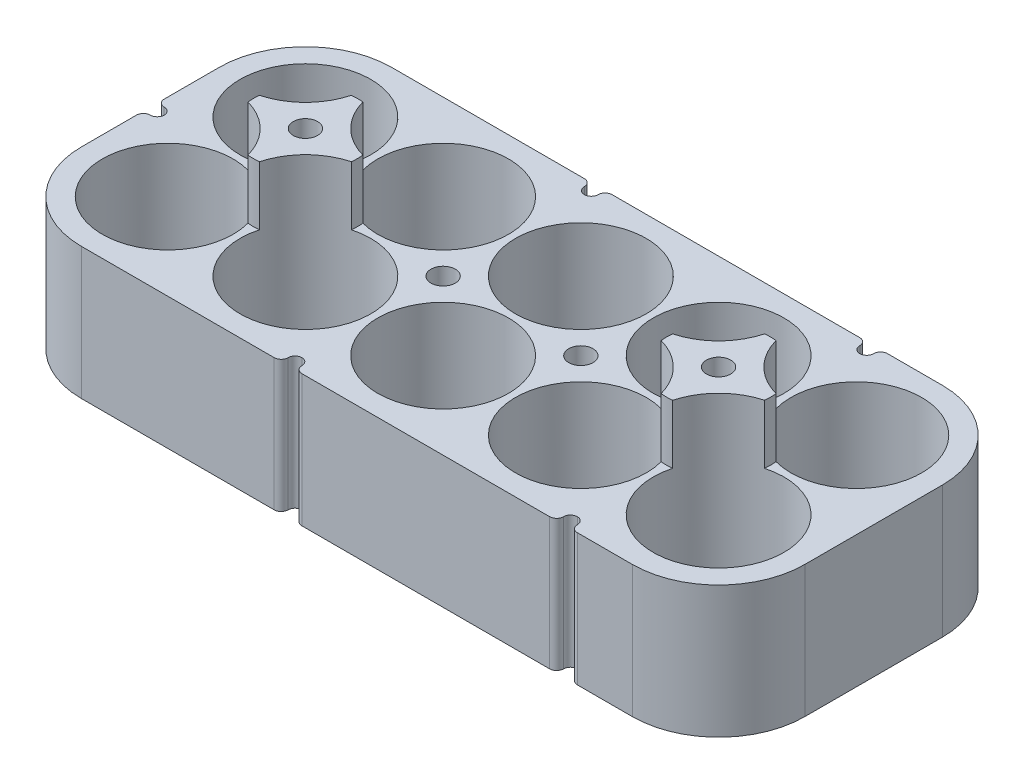
SolidWorks part; units mm, degrees
ref_plane "Front Plane" through (0, 0, 0) normal (0, 0, 1) x (1, 0, 0)
ref_plane "Top Plane" through (0, 0, 0) normal (0, 1, 0) x (1, 0, 0)
ref_plane "Right Plane" through (0, 0, 0) normal (1, 0, 0) x (0, 0, -1)
sketch "Sketch2" plane through (0, 0, 0) normal (0, 1, 0) x (1, 0, 0)
  line L0 (-39.7, 9.925) -> (-19.85, 9.925) construction
  line L1 (-19.85, 9.925) -> (0, 9.925) construction
  line L2 (0, 9.925) -> (19.85, 9.925) construction
  line L3 (19.85, 9.925) -> (39.7, 9.925) construction
  line L4 (39.7, 9.925) -> (39.7, -9.925) construction
  line L5 (39.7, -9.925) -> (19.85, -9.925) construction
  line L6 (19.85, -9.925) -> (0, -9.925) construction
  line L7 (0, -9.925) -> (-19.85, -9.925) construction
  line L8 (-39.7, 9.925) -> (-39.7, -9.925) construction
  line L9 (-39.7, -9.925) -> (-19.85, -9.925) construction
  line L10 (-39.7, 9.925) -> (39.7, -9.925) construction
  line L11 (-30.275, 9.925) -> (-29.275, 9.925) construction
  line L16 (-39.7, 0.5) -> (-39.7, -0.5) construction
  line L17 (-39.7, 22.35) -> (39.7, 22.35)
  line L19 (52.125, -9.925) -> (52.125, 9.925)
  line L20 (39.7, -22.35) -> (-39.7, -22.35)
  line L21 (-52.125, -9.925) -> (-52.125, 9.925)
  line L22 (-39.7, -9.925) -> (-52.125, -9.925) construction
  circle A0 centre (-39.7, 9.925) radius 9.425
  circle A1 centre (-19.85, 9.925) radius 9.425
  circle A2 centre (-39.7, -9.925) radius 9.425
  circle A3 centre (-19.85, -9.925) radius 9.425
  circle A4 centre (0, 9.925) radius 9.425
  circle A5 centre (0, -9.925) radius 9.425
  circle A6 centre (19.85, 9.925) radius 9.425
  circle A7 centre (19.85, -9.925) radius 9.425
  circle A8 centre (39.7, 9.925) radius 9.425
  circle A9 centre (39.7, -9.925) radius 9.425
  circle A10 centre (-39.7, 9.925) radius 12.425
  circle A11 centre (-39.7, -9.925) radius 12.425
  circle A12 centre (39.7, -9.925) radius 12.425
  circle A13 centre (39.7, 9.925) radius 12.425
  dimension "D1" = 18.85
  dimension "D2" = 1
  dimension "D3" = 1
  dimension "D4" = 3
extrude "Boss-Extrude1" add sketch "Sketch2" along normal blind 2.5 contours A13 L17 A10 A1 A11 A3 L20 A12 A7 A6 A5 A4 | A12 A13 A6 A8 | A13 A9 A12 A7 | A13 A12 L19 | A9 A13 A12 A8 | A11 A10 L21 | A11 A10 A1 A0 | A3 A11 A10 A2 | A10 A11 A0 A2 region at (-32.8744, 0, -19.9125) region at (0, 0, 0) region at (48.2539, 0, -18.4789) region at (-50.7094, 0, 0) region at (50.7094, 0, 0) region at (-50.5254, 0, 4.5259) region at (-39.7, 0, 0) region at (48.2539, 0, 18.4789) region at (39.7, 0, 0)
sketch "Sketch7" plane through (0, 0, 0) normal (0, 1, 0) x (1, 0, 0)
  line L0 (-29.775, 0) -> (-9.925, 0) construction
  line L1 (-9.925, 0) -> (9.925, 0) construction
  line L2 (9.925, 0) -> (29.775, 0) construction
  circle A1 centre (-29.775, 0) radius 3
  circle A2 centre (-9.925, 0) radius 1.75
  circle A3 centre (9.925, 0) radius 1.75
  circle A4 centre (29.775, 0) radius 3
  circle A5 centre (-29.775, 0) radius 4.6111 construction
  circle A7 centre (-39.7, 9.925) radius 9.425 construction
  circle A8 centre (-19.85, -9.925) radius 9.425 construction
  dimension "D1" = 6
  dimension "D2" = 3.5
extrude "Cut-Extrude3" cut sketch "Sketch7" along normal through all both and the other way through all
sketch "Sketch9" plane through (0, 2.5, 0) normal (0, 1, 0) x (1, 0, 0)
  line L0 (39.7, -22.35) -> (-39.7, -22.35)
  line L1 (-52.125, -9.925) -> (-52.125, 9.925)
  line L2 (-39.7, 22.35) -> (39.7, 22.35)
  line L3 (52.125, 9.925) -> (52.125, -9.925)
  line L4 (6.4609, 0) -> (-6.4609, 0) construction
  line L5 (6.4609, 0) -> (8.1929, -3)
  line L6 (8.1929, -3) -> (11.6571, -3)
  line L7 (11.6571, -3) -> (13.3891, 0)
  line L8 (13.3891, 0) -> (11.6571, 3)
  line L9 (11.6571, 3) -> (8.1929, 3)
  line L10 (8.1929, 3) -> (6.4609, 0)
  line L11 (-6.4609, 0) -> (-8.1929, 3)
  line L12 (-8.1929, 3) -> (-11.6571, 3)
  line L13 (-11.6571, 3) -> (-13.3891, 0)
  line L14 (-13.3891, 0) -> (-11.6571, -3)
  line L15 (-11.6571, -3) -> (-8.1929, -3)
  line L16 (-8.1929, -3) -> (-6.4609, 0)
  circle A0 centre (39.7, -9.925) radius 9.425
  circle A1 centre (19.85, -9.925) radius 9.425
  circle A2 centre (0, -9.925) radius 9.425
  circle A3 centre (-19.85, -9.925) radius 9.425
  circle A4 centre (-39.7, -9.925) radius 9.425
  circle A5 centre (-39.7, 9.925) radius 9.425
  circle A6 centre (-19.85, 9.925) radius 9.425
  circle A7 centre (0, 9.925) radius 9.425
  circle A8 centre (19.85, 9.925) radius 9.425
  circle A9 centre (39.7, 9.925) radius 9.425
  circle A10 centre (39.7, 9.925) radius 9.425 construction
  circle A11 centre (19.85, 9.925) radius 9.425 construction
  circle A12 centre (0, 9.925) radius 9.425 construction
  circle A13 centre (-19.85, 9.925) radius 9.425 construction
  circle A14 centre (-39.7, 9.925) radius 9.425 construction
  circle A15 centre (39.7, -9.925) radius 9.425 construction
  circle A16 centre (19.85, -9.925) radius 9.425 construction
  circle A17 centre (0, -9.925) radius 9.425 construction
  circle A18 centre (-19.85, -9.925) radius 9.425 construction
  circle A19 centre (-39.7, -9.925) radius 9.425 construction
  arc A20 (52.125, -9.925) -> (39.7, -22.35) centre (39.7, -9.925) cw
  arc A21 (-52.125, -9.925) -> (-39.7, -22.35) centre (-39.7, -9.925) ccw
  arc A22 (-52.125, 9.925) -> (-39.7, 22.35) centre (-39.7, 9.925) cw
  arc A23 (39.7, 22.35) -> (52.125, 9.925) centre (39.7, 9.925) cw
  circle A24 centre (29.775, 0) radius 3
  circle A25 centre (-29.775, 0) radius 3
  circle A26 centre (29.775, 0) radius 3 construction
  circle A27 centre (-29.775, 0) radius 3 construction
  circle A28 centre (9.925, 0) radius 3 construction
  circle A29 centre (9.925, 0) radius 1.75 construction
  circle A30 centre (-9.925, 0) radius 3 construction
  circle A31 centre (-9.925, 0) radius 1.75 construction
  dimension "D1" = 6
extrude "Boss-Extrude2" add sketch "Sketch9" along normal blind 3
sketch "Sketch11" plane through (0, 5.5, 0) normal (0, 1, 0) x (1, 0, 0)
  line L4 (39.7, -22.35) -> (-39.7, -22.35)
  line L17 (-52.125, -9.925) -> (-52.125, 9.925)
  line L18 (-39.7, 22.35) -> (39.7, 22.35)
  line L19 (52.125, 9.925) -> (52.125, -9.925)
  circle A10 centre (39.7, -9.925) radius 9.425
  circle A11 centre (19.85, -9.925) radius 9.425
  circle A12 centre (0, -9.925) radius 9.425
  circle A13 centre (-19.85, -9.925) radius 9.425
  circle A14 centre (-39.7, -9.925) radius 9.425
  circle A15 centre (-39.7, 9.925) radius 9.425
  circle A16 centre (-19.85, 9.925) radius 9.425
  circle A17 centre (0, 9.925) radius 9.425
  circle A18 centre (19.85, 9.925) radius 9.425
  circle A19 centre (39.7, 9.925) radius 9.425
  circle A26 centre (29.775, 0) radius 3
  circle A27 centre (-29.775, 0) radius 3
  circle A28 centre (-9.925, 0) radius 1.75
  circle A29 centre (9.925, 0) radius 1.75
  circle A30 centre (39.7, -9.925) radius 9.425 construction
  circle A31 centre (19.85, -9.925) radius 9.425 construction
  circle A32 centre (0, -9.925) radius 9.425 construction
  circle A33 centre (-19.85, -9.925) radius 9.425 construction
  circle A34 centre (-39.7, -9.925) radius 9.425 construction
  circle A35 centre (-39.7, 9.925) radius 9.425 construction
  circle A36 centre (-19.85, 9.925) radius 9.425 construction
  circle A37 centre (0, 9.925) radius 9.425 construction
  circle A38 centre (19.85, 9.925) radius 9.425 construction
  circle A39 centre (39.7, 9.925) radius 9.425 construction
  circle A40 centre (29.775, 0) radius 3 construction
  circle A41 centre (9.925, 0) radius 1.75 construction
  circle A42 centre (-9.925, 0) radius 1.75 construction
  circle A43 centre (-29.775, 0) radius 3 construction
  arc A44 (39.7, -22.35) -> (52.125, -9.925) centre (39.7, -9.925) ccw
  arc A45 (52.125, 9.925) -> (39.7, 22.35) centre (39.7, 9.925) ccw
  arc A46 (-39.7, 22.35) -> (-52.125, 9.925) centre (-39.7, 9.925) ccw
  arc A47 (-52.125, -9.925) -> (-39.7, -22.35) centre (-39.7, -9.925) ccw
extrude "Boss-Extrude3" add sketch "Sketch11" along normal blind 6
sketch "Sketch12" plane through (0, 11.5, 0) normal (0, 1, 0) x (1, 0, 0)
  line L0 (39.7, -22.35) -> (-39.7, -22.35)
  line L1 (-52.125, -9.925) -> (-52.125, 9.925)
  line L2 (-39.7, 22.35) -> (39.7, 22.35)
  line L3 (52.125, 9.925) -> (52.125, -9.925)
  circle A0 centre (39.7, -9.925) radius 9.425
  circle A1 centre (19.85, -9.925) radius 9.425
  circle A2 centre (0, -9.925) radius 9.425
  circle A3 centre (-19.85, -9.925) radius 9.425
  circle A4 centre (-39.7, -9.925) radius 9.425
  circle A5 centre (-39.7, 9.925) radius 9.425
  circle A6 centre (-19.85, 9.925) radius 9.425
  circle A7 centre (0, 9.925) radius 9.425
  circle A8 centre (19.85, 9.925) radius 9.425
  circle A9 centre (39.7, 9.925) radius 9.425
  circle A10 centre (39.7, 9.925) radius 9.425 construction
  circle A11 centre (19.85, 9.925) radius 9.425 construction
  circle A12 centre (0, 9.925) radius 9.425 construction
  circle A13 centre (-19.85, 9.925) radius 9.425 construction
  circle A14 centre (-39.7, 9.925) radius 9.425 construction
  circle A15 centre (39.7, -9.925) radius 9.425 construction
  circle A16 centre (19.85, -9.925) radius 9.425 construction
  circle A17 centre (0, -9.925) radius 9.425 construction
  circle A18 centre (-19.85, -9.925) radius 9.425 construction
  circle A19 centre (-39.7, -9.925) radius 9.425 construction
  circle A20 centre (29.775, 0) radius 1.75
  circle A21 centre (9.925, 0) radius 1.75
  circle A22 centre (-9.925, 0) radius 1.75
  circle A23 centre (-29.775, 0) radius 1.75
  circle A24 centre (9.925, 0) radius 1.75 construction
  circle A25 centre (-9.925, 0) radius 1.75 construction
  circle A26 centre (29.775, 0) radius 3 construction
  circle A27 centre (-29.775, 0) radius 3 construction
  arc A28 (39.7, -22.35) -> (52.125, -9.925) centre (39.7, -9.925) ccw
  arc A29 (52.125, 9.925) -> (39.7, 22.35) centre (39.7, 9.925) ccw
  arc A30 (-39.7, 22.35) -> (-52.125, 9.925) centre (-39.7, 9.925) ccw
  arc A31 (-52.125, -9.925) -> (-39.7, -22.35) centre (-39.7, -9.925) ccw
extrude "Boss-Extrude4" add sketch "Sketch12" along normal blind 16
ref_plane "Plane1" through (0, 22.5, 0) normal (0, 1, 0) x (1, 0, 0)
sketch "Sketch13" plane through (0, 22.5, 0) normal (0, 1, 0) x (1, 0, 0)
  line L0 (-26.3109, 0) -> (26.3109, 0) construction
  line L1 (-28.0429, -3) -> (-26.3109, 0)
  line L2 (-26.3109, 0) -> (-28.0429, 3)
  line L3 (-28.0429, 3) -> (-31.5071, 3)
  line L4 (-31.5071, 3) -> (-33.2391, 0)
  line L5 (-33.2391, 0) -> (-31.5071, -3)
  line L6 (-31.5071, -3) -> (-28.0429, -3)
  line L7 (28.0429, -3) -> (31.5071, -3)
  line L8 (31.5071, -3) -> (33.2391, 0)
  line L9 (33.2391, 0) -> (31.5071, 3)
  line L10 (31.5071, 3) -> (28.0429, 3)
  line L11 (28.0429, 3) -> (26.3109, 0)
  line L12 (26.3109, 0) -> (28.0429, -3)
  circle A0 centre (-29.775, 0) radius 3 construction
  circle A1 centre (29.775, 0) radius 3 construction
  dimension "D1" = 6
extrude "Cut-Extrude4" cut sketch "Sketch13" against normal blind 3
sketch "Sketch14" plane through (0, 27.5, 0) normal (0, 1, 0) x (1, 0, 0)
  line L0 (-52.125, 9.925) -> (-52.125, -9.925) construction
  line L1 (-52.125, 1) -> (-50.125, 1)
  line L2 (-52.125, 1) -> (-52.125, -1)
  line L3 (-52.125, -1) -> (-50.125, -1)
  line L4 (-50.125, 1) -> (-50.125, -1)
  line L5 (-39.7, -22.35) -> (39.7, -22.35) construction
  line L6 (28.775, -22.35) -> (30.775, -22.35)
  line L7 (28.775, -22.35) -> (28.775, -20.35)
  line L8 (28.775, -20.35) -> (30.775, -20.35)
  line L9 (30.775, -22.35) -> (30.775, -20.35)
  line L10 (39.7, 22.35) -> (-39.7, 22.35) construction
  line L11 (-10.925, -22.35) -> (-8.925, -22.35)
  line L12 (-10.925, -22.35) -> (-10.925, -20.35)
  line L13 (-10.925, -20.35) -> (-8.925, -20.35)
  line L14 (-8.925, -22.35) -> (-8.925, -20.35)
  line L15 (-10.925, 22.35) -> (-8.925, 22.35)
  line L16 (-10.925, 22.35) -> (-10.925, 20.35)
  line L17 (-10.925, 20.35) -> (-8.925, 20.35)
  line L18 (-8.925, 22.35) -> (-8.925, 20.35)
  line L19 (-9.925, 0) -> (-9.925, -20.35) construction
  line L20 (28.775, 22.35) -> (30.775, 22.35)
  line L21 (28.775, 22.35) -> (28.775, 20.35)
  line L22 (28.775, 20.35) -> (30.775, 20.35)
  line L23 (30.775, 22.35) -> (30.775, 20.35)
  line L24 (-9.925, 0) -> (-9.925, 20.35) construction
  line L25 (29.775, 0) -> (29.775, 20.35) construction
  line L26 (29.775, 0) -> (29.775, -20.35) construction
  line L27 (-50.125, 0) -> (-29.775, 0) construction
  dimension "D1" = 2
  dimension "D2" = 2
extrude "Cut-Extrude5" cut sketch "Sketch14" against normal through all
fillet "Fillet1" radius 1 30 edges at (28.775, 27.5, -21.35) (30.775, 27.5, -21.35) (-10.925, 27.5, -21.35) (-8.925, 27.5, -21.35) (-51.125, 27.5, 1) (-51.125, 27.5, -1) (30.775, 27.5, 21.35) (28.775, 27.5, 21.35) (-8.925, 27.5, 21.35) (-10.925, 27.5, 21.35) (28.775, 13.75, -20.35) (30.775, 13.75, -20.35) (-10.925, 13.75, -20.35) (-8.925, 13.75, -20.35) (-50.125, 13.75, 1) (-50.125, 13.75, -1) (30.775, 13.75, 20.35) (28.775, 13.75, 20.35) (30.775, 13.75, -22.35) (28.775, 13.75, -22.35) (-8.925, 13.75, -22.35) (-10.925, 13.75, -22.35) (-52.125, 13.75, 1) (-52.125, 13.75, -1) (30.775, 13.75, 22.35) (28.775, 13.75, 22.35) (-8.925, 13.75, 22.35) (-8.925, 13.75, 20.35) (-10.925, 13.75, 20.35) (-10.925, 13.75, 22.35)
ref_plane "Plane2" through (0, 19, 0) normal (0, 1, 0) x (1, 0, 0)
sketch "Sketch15" plane through (0, 19, 0) normal (0, 1, 0) x (1, 0, 0)
  line L0 (-52.125, 9.925) -> (-52.125, 2) construction
  line L1 (-52.125, 22.35) -> (52.125, 22.35)
  line L2 (-52.125, 22.35) -> (-52.125, -22.35)
  line L3 (-52.125, -22.35) -> (52.125, -22.35)
  line L4 (52.125, 22.35) -> (52.125, -22.35)
  line L5 (52.125, -9.925) -> (52.125, 9.925) construction
  line L6 (27.775, 22.35) -> (-7.925, 22.35) construction
  line L7 (-7.925, -22.35) -> (27.775, -22.35) construction
  circle A0 centre (-29.775, 0) radius 7.5
  circle A1 centre (29.775, 0) radius 7.5
  dimension "D1" = 15
extrude "Cut-Extrude6" cut sketch "Sketch15" along normal through all
